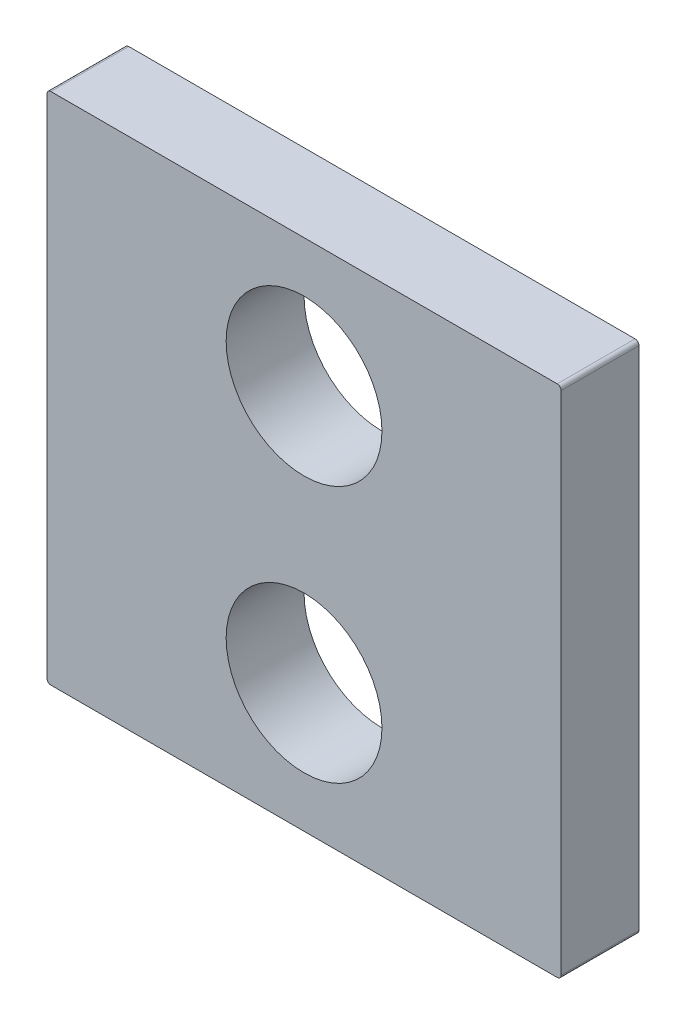
SolidWorks part; units mm, degrees
material "Beech"
ref_plane "Front Plane" through (0, 0, 0) normal (0, 0, 1) x (1, 0, 0)
ref_plane "Top Plane" through (0, 0, 0) normal (0, 1, 0) x (1, 0, 0)
ref_plane "Right Plane" through (0, 0, 0) normal (1, 0, 0) x (0, 0, -1)
sketch "Sketch1" plane through (0, 0, 0) normal (0, 0, 1) x (1, 0, 0)
  line L0 (151.0175, 69.0432) -> (151.0175, -13.5068)
  line L5 (151.6525, -14.1418) -> (234.2025, -14.1418)
  line L6 (234.8375, -13.5068) -> (234.8375, 69.0432)
  line L7 (234.2025, 69.6782) -> (151.6525, 69.6782)
  line L9 (148.4775, 69.0432) -> (148.4775, -13.5068) construction
  line L10 (234.2025, 72.2182) -> (151.6525, 72.2182) construction
  line L11 (237.3775, -13.5068) -> (237.3775, 69.0432) construction
  line L12 (151.6525, -16.6818) -> (234.2025, -16.6818) construction
  arc A4 (151.0175, -13.5068) -> (151.6525, -14.1418) centre (151.6525, -13.5068) ccw
  arc A5 (234.2025, -14.1418) -> (234.8375, -13.5068) centre (234.2025, -13.5068) ccw
  arc A6 (234.8375, 69.0432) -> (234.2025, 69.6782) centre (234.2025, 69.0432) ccw
  arc A7 (151.6525, 69.6782) -> (151.0175, 69.0432) centre (151.6525, 69.0432) ccw
  arc A8 (151.6525, 72.2182) -> (148.4775, 69.0432) centre (151.6525, 69.0432) ccw construction
  arc A9 (237.3775, 69.0432) -> (234.2025, 72.2182) centre (234.2025, 69.0432) ccw construction
  arc A10 (234.2025, -16.6818) -> (237.3775, -13.5068) centre (234.2025, -13.5068) ccw construction
  arc A11 (148.4775, -13.5068) -> (151.6525, -16.6818) centre (151.6525, -13.5068) ccw construction
  point P0 (237.1957, -14.5658)
  dimension "D1" = 2.54
extrude "Boss-Extrude1" add sketch "Sketch1" against normal blind 12.7
hole_wizard "1 (1) Diameter Hole1" positions "Sketch3" profile "Sketch4" hole size "1" standard "ANSI Inch" end condition up to next
sketch "Sketch3" plane through (0, 0, 0) normal (0, 0, 1) x (1, 0, 0)
  line L0 (192.9275, 69.6782) -> (192.9275, 27.7682) construction
  line L1 (234.2025, 69.6782) -> (151.6525, 69.6782) construction
  line L2 (192.9275, 27.7682) -> (192.9275, -14.1418) construction
  line L4 (151.6525, -14.1418) -> (234.2025, -14.1418) construction
  point P11 (192.9275, 48.7232)
  point P13 (192.9275, 6.8132)
  point P14 (192.9275, -14.1418)
sketch "Sketch4" plane through (192.9275, 6.8132, 0) normal (1, 0, 0) x (0, -1, 0)
  line L0 (0, 0) -> (0, 12.7)
  line L1 (0, 12.7) -> (12.7, 12.7)
  line L2 (12.7, 12.7) -> (12.7, 0)
  line L5 (12.7, 0) -> (0, 0)
  line L11 (0, -6.35) -> (0, 107.95) construction
  dimension "Thru Hole Dia." = 25.4
  dimension "Thru Hole Depth" = 12.7
